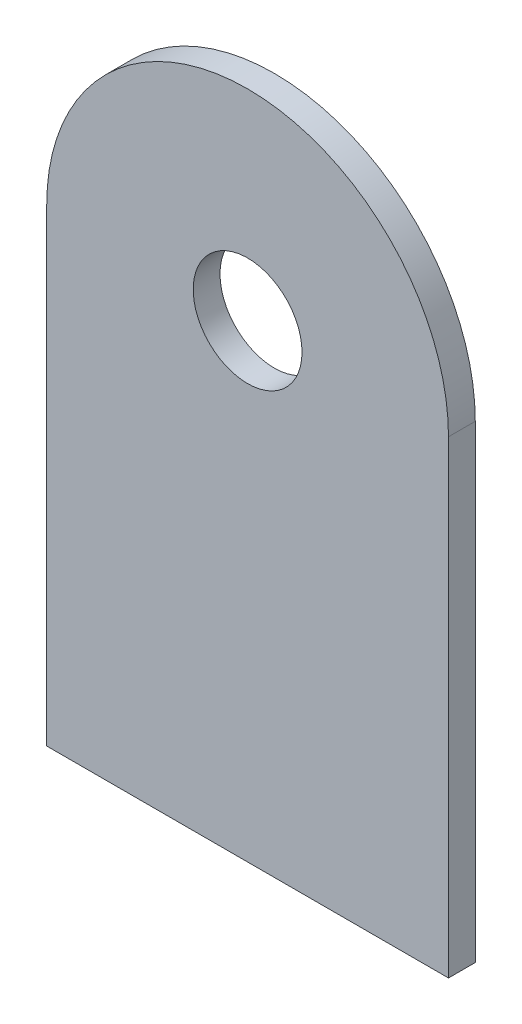
SolidWorks part; units mm, degrees
ref_plane "Front Plane" through (0, 0, 0) normal (0, 0, 1) x (1, 0, 0)
ref_plane "Top Plane" through (0, 0, 0) normal (0, 1, 0) x (1, 0, 0)
ref_plane "Right Plane" through (0, 0, 0) normal (1, 0, 0) x (0, 0, -1)
sketch "Sketch2" plane through (0, 0, 0) normal (0, 0, 1) x (1, 0, 0)
  line L1 (-7.5274, -8.2545) -> (11.5226, -8.2545)
  line L2 (-7.5274, -8.2545) -> (-7.5274, 13.9705)
  line L4 (11.5226, -8.2545) -> (11.5226, 13.9705)
  arc A0 (-7.5274, 13.9705) -> (11.5226, 13.9705) centre (1.9976, 13.9705) cw
  circle A1 centre (1.9976, 13.9705) radius 2.5797
  dimension "D3" = 5.1594
  dimension "D1" = 19.05
  dimension "D2" = 22.225
extrude "Boss-Extrude1" add sketch "Sketch2" along normal blind 1.27 contours A0 L4 L1 L2
sketch "Sketch3" plane through (0, 0, 1.27) normal (0, 0, 1) x (1, 0, 0)
  circle A0 centre (1.9976, 13.9705) radius 2.5797
  dimension "D1" = 5.1594
extrude "Cut-Extrude1" cut sketch "Sketch3" against normal blind 2.54
